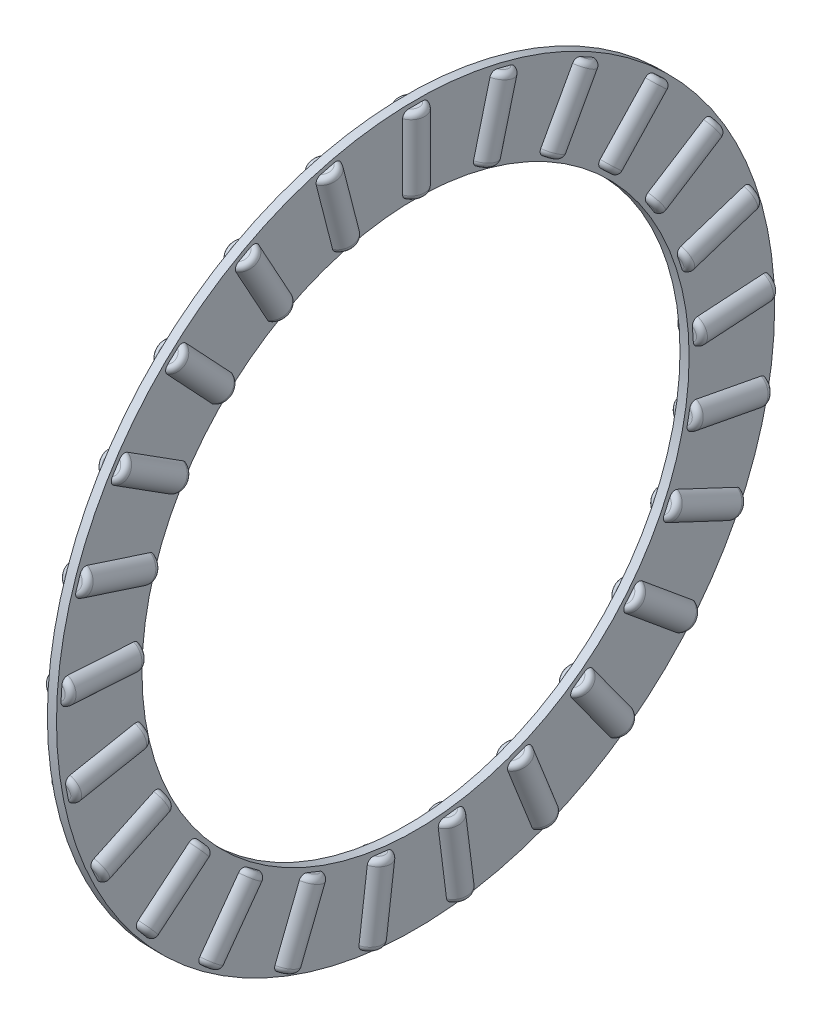
SolidWorks part; units mm, degrees
ref_plane "Plane1" through (0, 0, 0) normal (0, 0, 1) x (1, 0, 0)
ref_plane "Plane2" through (0, 0, 0) normal (0, 1, 0) x (1, 0, 0)
ref_plane "Plane3" through (0, 0, 0) normal (1, 0, 0) x (0, 0, -1)
sketch "Clipboard" plane through (0, 0, 0) normal (0, 0, 1) x (1, 0, 0)
  line L0 (-10, 0) -> (10, 0) construction
  line L1 (0, 0) -> (20.2657, -9.45)
  line L2 (0, 0) -> (41.9167, 19.5461)
  line L3 (0, 0) -> (20.2657, -9.45)
  line L4 (0, 0) -> (-22.3471, -0.7804)
  dimension "BallCLRad" = 46.25
sketch "CagSpiSke" plane through (0, 0, 0) normal (0, 0, 1) x (1, 0, 0)
  line L5 (-34.925, 0) -> (34.925, 0) construction
  line L6 (-0.6667, 52.5) -> (0.6667, 52.5)
  line L7 (-0.6667, 52.5) -> (-0.6667, 40)
  line L8 (-0.6667, 40) -> (0.6667, 40)
  line L9 (0.6667, 52.5) -> (0.6667, 40)
  dimension "ID" = 80
  dimension "OD" = 105
revolve "CageSpine" add sketch "CagSpiSke" angle 360 about L5 reverse direction yes
ref_axis "Axis1" through (-50, 0, 0) along (1, 0, 0)
sketch "RolDetSke" plane through (0, 0, 0) normal (0, 0, 1) x (1, 0, 0)
  line L0 (0, 33.02) -> (0, 55.88) construction
  line L3 (0, 51.875) -> (1.2, 51.875)
  line L4 (0, 51.875) -> (0, 40.625)
  line L5 (0, 40.625) -> (1.2, 40.625)
  line L6 (2, 51.075) -> (2, 41.425)
  arc A0 (2, 41.425) -> (1.2, 40.625) centre (1.2, 41.425) cw
  arc A1 (1.2, 51.875) -> (2, 51.075) centre (1.2, 51.075) cw
  dimension "offset" = 40.625
  dimension "Roller_diameter" = 4
  dimension "Cyl_Len" = 11.25
revolve "RollerDetailed" add sketch "RolDetSke" angle 360 about L0 reverse direction yes
pattern_circular "RollersDetailed" count 25 every 14.4 about axis through (-50, 0, 0) along (1, 0, 0) of "RollerDetailed"
sketch "RolSimSke" plane through (0, 0, 0) normal (0, 0, 1) x (1, 0, 0)
  line L1 (-17.78, 0) -> (12.7, 0) construction
  line L3 (-1.2, 51.875) -> (1.2, 51.875)
  line L4 (-2, 51.075) -> (-2, 41.425)
  line L5 (-1.2, 40.625) -> (1.2, 40.625)
  line L6 (2, 51.075) -> (2, 41.425)
  arc A0 (-2, 41.425) -> (-1.2, 40.625) centre (-1.2, 41.425) ccw
  arc A1 (-1.2, 51.875) -> (-2, 51.075) centre (-1.2, 51.075) ccw
  arc A2 (2, 51.075) -> (1.2, 51.875) centre (1.2, 51.075) ccw
  arc A3 (1.2, 40.625) -> (2, 41.425) centre (1.2, 41.425) ccw
  dimension "Halfdia" = 2
  dimension "offset" = 40.625
  dimension "Roller_diameter" = 4
  dimension "Cyl_Len" = 11.25
revolve "RollersSimplified" [suppressed] add sketch "RolSimSke" angle 360 about L1
equation "\"BallCLRad@Clipboard\" =  ( \"OD@CagSpiSke\" + \"ID@CagSpiSke\" )  / 4"
equation "\"offset@RolSimSke\" = \"BallCLRad@Clipboard\" - \"Cyl_Len@RolSimSke\" / 2"
equation "\"offset@RolDetSke\" = \"BallCLRad@Clipboard\" - \"Cyl_Len@RolDetSke\" / 2"
equation "\"Thickness@CagSpiSke\" =  \"Roller_diameter@RolDetSke\" / 3"
equation "\"HalfThick@CagSpiSke\" = \"Thickness@CagSpiSke\" / 2"
equation "\"radius@RolDetSke\" =  ( \"Roller_diameter@RolDetSke\" - \"Thickness@CagSpiSke\" )  * 0.6 / 2"
equation "\"Roller_diameter@RolSimSke\" = \"Roller_diameter@RolDetSke\""
equation "\"Cyl_Len@RolSimSke\" = \"Cyl_Len@RolDetSke\""
equation "\"Rol_rad@RolSimSke\" = \"radius@RolDetSke\""
equation "\"Halfdia@RolSimSke\" = \"Roller_diameter@RolSimSke\" / 2"
equation "\"Max_count@Clipboard\" = int( 3.14159265 / atn(( \"Roller_diameter@RolDetSke\" / 2) / sqr( \"offset@RolDetSke\"  *  \"offset@RolDetSke\" - ( \"Roller_diameter@RolDetSke\" / 2) *  ( \"Roller_diameter@RolDetSke\" / 2))))"
equation "\"Max_count@Clipboard\" = ((sgn( \"Max_count@Clipboard\" - \"Count@Clipboard\" )-1)*( \"Max_count@Clipboard\" - \"Count@Clipboard\" ))/-2+ \"Count@Clipboard\""
equation "\"Count@RollersDetailed\" = int( \"Show_count@Clipboard\" ) "
equation "\"Count@RollersDetailed\" = ((sgn( \"Count@RollersDetailed\" - \"Max_count@Clipboard\" )-1)*( \"Count@RollersDetailed\" - \"Max_count@Clipboard\" ))/-2+ \"Max_count@Clipboard\""
equation "\"Count@RollersDetailed\" = ((sgn( \"Count@RollersDetailed\" - \"Min_count@Clipboard\" )+1)*( \"Count@RollersDetailed\" - \"Min_count@Clipboard\"))/2 +\"Min_count@Clipboard\""
equation "\"Angle@RollersDetailed\" = 360.0 / \"Max_count@Clipboard\""
